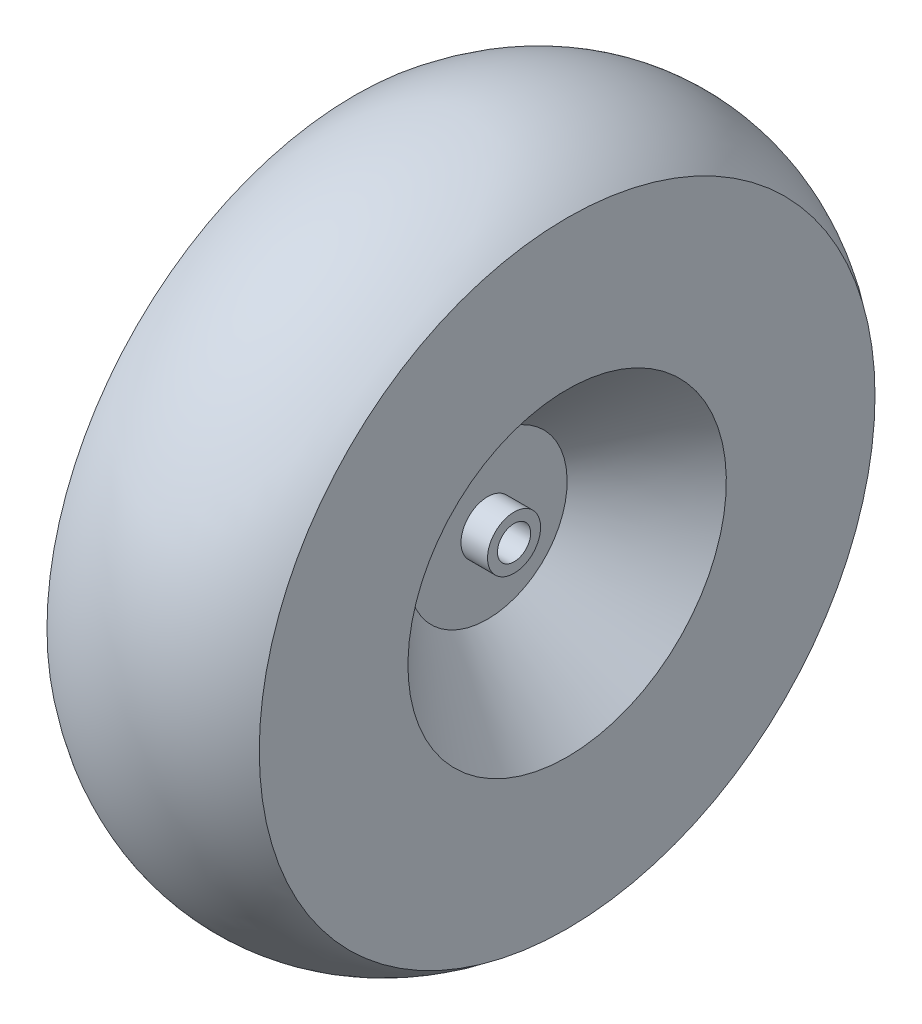
SolidWorks part; units mm, degrees
ref_plane "Front Plane" through (0, 0, 0) normal (0, 0, 1) x (1, 0, 0)
ref_plane "Top Plane" through (0, 0, 0) normal (0, 1, 0) x (1, 0, 0)
ref_plane "Right Plane" through (0, 0, 0) normal (1, 0, 0) x (0, 0, -1)
sketch "Sketch7" plane through (0, 0, 0) normal (0, 0, 1) x (1, 0, 0)
  line L4 (25.4, 7.9375) -> (25.4, 12.7)
  line L6 (12.7, 12.7) -> (25.4, 12.7)
  line L8 (12.7, 12.7) -> (12.7, 38.1)
  line L11 (-25.4, 0) -> (25.4, 0) construction
  line L12 (12.7, 38.1) -> (50.8, 76.2)
  line L13 (50.8, 76.2) -> (50.8, 147.3587)
  line L16 (25.4, 7.9375) -> (-25.4, 7.9375)
  line L44 (-12.7, 12.7) -> (12.7, 12.7) construction
  line L49 (-50.8, 147.3587) -> (50.8, 147.3587) construction
  line L53 (-50.8, 76.2) -> (-50.8, 147.3587)
  line L54 (-12.7, 38.1) -> (-50.8, 76.2)
  line L55 (-12.7, 12.7) -> (-12.7, 38.1)
  line L56 (-12.7, 12.7) -> (-25.4, 12.7)
  line L57 (-25.4, 7.9375) -> (-25.4, 12.7)
  ellipse E1 centre (0, 79.5701) end of major axis (0, -5.9598) minor radius 83.3088 (50.8, 147.3587) -> (-50.8, 147.3587) ccw
  point P5 (0, 0)
  point P6 (0, 12.7)
  point P8 (0, 147.3587)
  point P59 (50.8, 147.3587)
  dimension "D1" = 50.8
  dimension "D2" = 7.9375
  dimension "D3" = 101.6
  dimension "D4" = 76.2
  dimension "D5" = 165.1
  dimension "D6" = 45
  dimension "D8" = 25.4
  dimension "D9" = 12.7
revolve "Revolve6" add sketch "Sketch7" angle 360 about L11 region at (0, 98.9711, 0)
